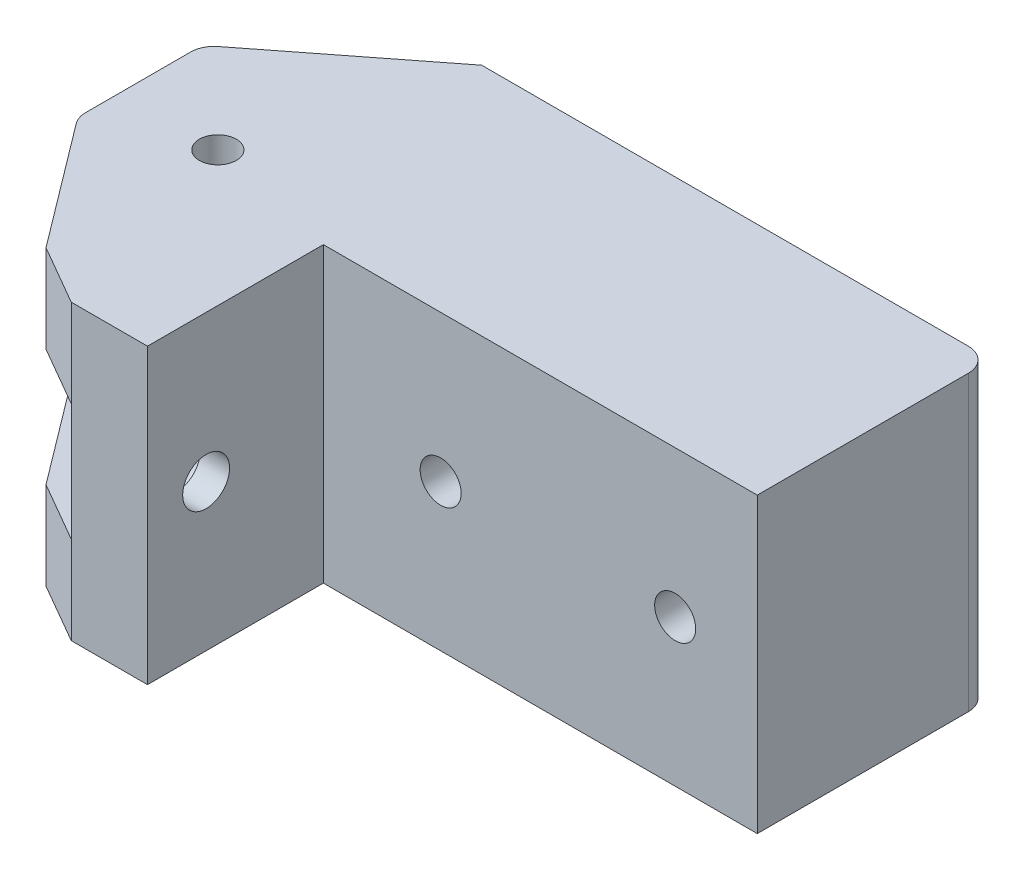
SolidWorks part; units mm, degrees
ref_plane "Front Plane" through (0, 0, 0) normal (0, 0, 1) x (1, 0, 0)
ref_plane "Top Plane" through (0, 0, 0) normal (0, 1, 0) x (1, 0, 0)
ref_plane "Right Plane" through (0, 0, 0) normal (1, 0, 0) x (0, 0, -1)
sketch "Sketch1" plane through (0, 0, 0) normal (0, 1, 0) x (1, 0, 0)
  line L0 (0, 0) -> (-43.5, 0)
  line L1 (-43.5, 0) -> (-43.5, -35) construction
  line L2 (-43.5, -35) -> (-37, -35)
  line L3 (-37, -35) -> (-37, -20)
  line L4 (-37, -20) -> (0, -20)
  line L5 (0, -20) -> (0, 0)
  line L6 (-43.5, 0) -> (-56.8853, -10.4577)
  line L7 (-56.8853, -10.4577) -> (-56.8853, -21.0577)
  line L8 (-56.8853, -21.0577) -> (-48.5962, -32.0577)
  line L9 (-48.5962, -32.0577) -> (-43.5, -35)
  line L10 (-43.5, -17.5) -> (-48.5, -17.5) construction
  circle A0 centre (-48.5, -17.5) radius 1.575
  dimension "D11" = 3.15
  dimension "D1" = 43.5
  dimension "D2" = 35
  dimension "D3" = 20
  dimension "D4" = 37
  dimension "D5" = 30
  dimension "D6" = 38
  dimension "D7" = 10.6
  dimension "D8" = 37
  dimension "D9" = 11
  dimension "D10" = 5
extrude "Boss-Extrude1" add sketch "Sketch1" along normal mid plane 25
sketch "Sketch2" plane through (0, 0, 35) normal (0, 0, 1) x (1, 0, 0)
  line L0 (-43.5, 12.5) -> (-43.5, -12.5) construction
  line L1 (-43.5, -5) -> (-56.8853, -5)
  line L2 (-43.5, -5) -> (-43.5, 5)
  line L3 (-43.5, 5) -> (-56.8853, 5)
  line L4 (-56.8853, -5) -> (-56.8853, 5)
  line L5 (-56.8853, 12.5) -> (-56.8853, -12.5) construction
  line L6 (-56.8853, 12.5) -> (-48.5962, 12.5) construction
  dimension "D1" = 7.5
  dimension "D2" = 10
extrude "Cut-Extrude1" cut sketch "Sketch2" against normal through all
sketch "Sketch3" plane through (0, 0, 20) normal (0, 0, 1) x (1, 0, 0)
  line L1 (0, 0) -> (-27, 0) construction
  line L2 (-37, 12.5) -> (-37, -12.5) construction
  circle A0 centre (-27, 0) radius 1.75
  circle A1 centre (-7, 0) radius 1.75
  dimension "D1" = 3.5
  dimension "D2" = 20
  dimension "D3" = 10
extrude "Cut-Extrude2" cut sketch "Sketch3" against normal blind 25
sketch "Sketch4" plane through (0, 0, 0) normal (0, 0, -1) x (-1, 0, 0)
  circle A0 centre (7, 0) radius 4
  circle A2 centre (27, 0) radius 4
extrude "Cut-Extrude3" cut sketch "Sketch4" against normal blind 4
fillet "Fillet1" radius 2 5 edges at (0, 0, 0) (-56.8853, 8.75, 10.4577) (-56.8853, 8.75, 21.0577) (-56.8853, -8.75, 21.0577) (-56.8853, -8.75, 10.4577)
sketch "Sketch5" plane through (-43.5, 0, 0) normal (-1, 0, 0) x (0, 0, 1)
  line L0 (30, 0) -> (35, 0) construction
  line L1 (35, -5) -> (35, 5) construction
  circle A0 centre (30, 0) radius 2
  point P2 (35, 0)
  dimension "D1" = 4
  dimension "D2" = 5
extrude "Cut-Extrude4" cut sketch "Sketch5" against normal through all
sketch "Sketch6" plane through (-43.5, 0, 0) normal (-1, 0, 0) x (0, 0, 1)
  circle A0 centre (30, 0) radius 4
  dimension "D1" = 8
extrude "Cut-Extrude5" cut sketch "Sketch6" against normal blind 4
